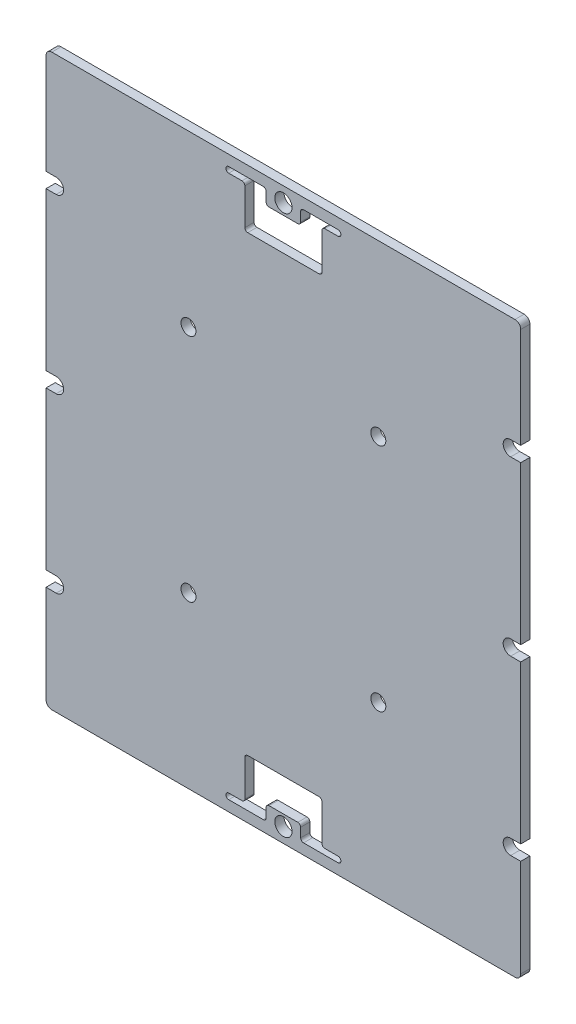
SolidWorks part; units mm, degrees
material "FR4_stuffedProtoboard"
ref_plane "Front Plane" through (0, 0, 0) normal (0, 0, 1) x (1, 0, 0)
ref_plane "Top Plane" through (0, 0, 0) normal (0, 1, 0) x (1, 0, 0)
ref_plane "Right Plane" through (0, 0, 0) normal (1, 0, 0) x (0, 0, -1)
sketch "Sketch2" plane through (0, 0, 0) normal (0, 0, 1) x (1, 0, 0)
  line L0 (39.5, 49.75) -> (-39.5, 49.75) construction
  line L1 (-41.5, 49.75) -> (41.5, 49.75) construction
  line L2 (-41.5, 49.75) -> (-41.5, -49.75) construction
  line L3 (-41.5, -49.75) -> (41.5, -49.75) construction
  line L4 (41.5, 49.75) -> (41.5, -49.75) construction
  line L5 (-41.5, 49.75) -> (41.5, -49.75) construction
  line L6 (-41.5, -49.75) -> (41.5, 49.75) construction
  line L7 (41.5, 51.75) -> (41.5, 40.35) construction
  line L8 (-41.5, 49.75) -> (41.5, 49.75) construction
  line L9 (41.5, 49.75) -> (41.5, -49.75) construction
  line L10 (-41.5, -49.75) -> (41.5, -49.75) construction
  line L11 (-41.5, 49.75) -> (-41.5, -49.75) construction
  line L12 (-37, -31.85) -> (37, -31.85) construction
  line L13 (-37, -30.25) -> (37, -30.25) construction
  line L14 (-37, -21.85) -> (37, -21.85) construction
  line L15 (-37, -20.25) -> (37, -20.25) construction
  line L16 (-37, -11.85) -> (37, -11.85) construction
  line L17 (-37, -10.25) -> (37, -10.25) construction
  line L18 (-37, -1.85) -> (37, -1.85) construction
  line L19 (-37, -0.25) -> (37, -0.25) construction
  line L20 (-37, 8.15) -> (37, 8.15) construction
  line L21 (-37, 9.75) -> (37, 9.75) construction
  line L22 (-37, 18.15) -> (37, 18.15) construction
  line L23 (-37, 19.75) -> (37, 19.75) construction
  line L24 (-37, 28.15) -> (37, 28.15) construction
  line L25 (-37, 29.75) -> (37, 29.75) construction
  line L26 (-37, 38.15) -> (37, 38.15) construction
  line L27 (-37, 39.75) -> (37, 39.75) construction
  line L28 (-37, -31.85) -> (37, -31.85) construction
  line L29 (-37, -30.25) -> (37, -30.25) construction
  line L30 (-37, -21.85) -> (37, -21.85) construction
  line L31 (-37, -20.25) -> (37, -20.25) construction
  line L32 (-37, -11.85) -> (37, -11.85) construction
  line L33 (-37, -10.25) -> (37, -10.25) construction
  line L34 (-37, -1.85) -> (37, -1.85) construction
  line L35 (-37, -0.25) -> (37, -0.25) construction
  line L36 (-37, 8.15) -> (37, 8.15) construction
  line L37 (-37, 9.75) -> (37, 9.75) construction
  line L38 (-37, 18.15) -> (37, 18.15) construction
  line L39 (-37, 19.75) -> (37, 19.75) construction
  line L40 (-37, 28.15) -> (37, 28.15) construction
  line L41 (-37, 29.75) -> (37, 29.75) construction
  line L42 (-37, 38.15) -> (37, 38.15) construction
  line L43 (-37, 39.75) -> (37, 39.75) construction
  line L44 (-37, -40.25) -> (37, -40.25) construction
  line L45 (-37, -41.85) -> (37, -41.85) construction
  line L46 (-41.5, 51.75) -> (-41.5, 40.35) construction
  line L47 (39.5, -49.75) -> (-39.5, -49.75) construction
  line L48 (41.5, -31.9) -> (41.5, -51.75) construction
  line L49 (-41.25, 49.5) -> (41.25, 49.5)
  line L50 (41.25, 49.5) -> (41.25, -49.5)
  line L51 (-41.25, -49.5) -> (41.25, -49.5)
  line L52 (-41.25, 49.5) -> (-41.25, -49.5)
  circle A0 centre (0, 46.95) radius 1.5 construction
  circle A1 centre (0, 46.95) radius 0.8 construction
  circle A2 centre (0, 46.95) radius 1.5 construction
  circle A3 centre (0, 46.95) radius 0.8
  circle A4 centre (-39.5, -30.25) radius 0.8 construction
  circle A5 centre (-39.5, -0.25) radius 0.8 construction
  circle A6 centre (-39.5, 29.75) radius 0.8 construction
  circle A7 centre (-39.5, -30.25) radius 0.8
  circle A8 centre (-39.5, -0.25) radius 0.8
  circle A9 centre (-39.5, 29.75) radius 0.8
  circle A10 centre (39.5, -30.25) radius 0.8 construction
  circle A11 centre (39.5, -0.25) radius 0.8 construction
  circle A12 centre (39.5, 29.75) radius 0.8 construction
  circle A13 centre (39.5, -30.25) radius 0.8
  circle A14 centre (39.5, -0.25) radius 0.8
  circle A15 centre (39.5, 29.75) radius 0.8
  circle A16 centre (0, -46.95) radius 0.8 construction
  circle A17 centre (0, -46.95) radius 0.8
  circle A18 centre (0, -46.95) radius 1.5 construction
  circle A19 centre (0, -46.95) radius 1.5
  circle A20 centre (-16.5, 20) radius 1.75 construction
  circle A21 centre (-16.5, 20) radius 0.8 construction
  circle A22 centre (-16.5, 20) radius 1.75 construction
  circle A23 centre (-16.5, 20) radius 0.8
  circle A24 centre (16.5, 20) radius 1.75 construction
  circle A25 centre (16.5, 20) radius 0.8 construction
  circle A26 centre (16.5, 20) radius 1.75 construction
  circle A27 centre (16.5, 20) radius 0.8
  circle A28 centre (16.5, -20) radius 1.75 construction
  circle A29 centre (-16.5, -20) radius 1.75 construction
  circle A30 centre (16.5, -20) radius 1.75 construction
  circle A31 centre (-16.5, -20) radius 1.75 construction
  circle A32 centre (-16.5, -20) radius 0.8 construction
  circle A33 centre (-16.5, -20) radius 0.8
  circle A34 centre (16.5, -20) radius 0.8 construction
  circle A35 centre (16.5, -20) radius 0.8
  point P0 (0, 0)
  point P74 (0, -40.25)
  point P75 (0, -31.85)
  point P76 (0, -41.85)
  dimension "D2" = 10
  dimension "D3" = 1.6
  dimension "D1" = 0.25
extrude "pcb extrude" add sketch "Sketch2" along normal mid plane 1.6 contours L4 L1 L2 L3 A2 | A2 A3 | L2 L1 L4 L3 region at (0, 0.0296, 0)
sketch "endcap connector" plane through (0, 0, 0.8) normal (0, 0, 1) x (1, 0, 0)
  line L0 (-10.3489, -47.209) -> (-10.3489, -49.749) construction
  line L1 (-36.1289, -47.209) -> (-10.3489, -47.209) construction
  line L2 (-36.1289, -47.209) -> (-10.3489, -47.209)
  line L3 (-36.1289, -49.749) -> (-36.1289, -47.209) construction
  line L4 (-10.3489, -47.209) -> (-10.3489, -49.749)
  line L5 (-36.1289, -49.749) -> (-36.1289, -47.209)
  point P3 (-23.2389, -47.209)
sketch "connector locations" plane through (0, 0, 0.8) normal (0, 0, 1) x (1, 0, 0)
  line L0 (34.5, 45.75) -> (4.5, 45.75) construction
  line L1 (-2.5, 44.75) -> (2.5, 44.75) construction
  line L2 (-4.5, 45.75) -> (-34.5, 45.75) construction
  line L3 (34.5, 45.75) -> (4.5, 45.75)
  line L4 (-2.5, 44.75) -> (2.5, 44.75)
  line L5 (-4.5, 45.75) -> (-34.5, 45.75)
  line L6 (-37, 43.25) -> (-37, -43.25) construction
  line L7 (-37, 43.25) -> (-37, -43.25)
  line L8 (37, -43.25) -> (37, 43.25) construction
  line L9 (37, -43.25) -> (37, 43.25)
  line L10 (4.5, -45.75) -> (34.5, -45.75) construction
  line L11 (4.5, -45.75) -> (34.5, -45.75)
  line L12 (-34.5, -45.75) -> (-4.5, -45.75) construction
  line L13 (-2.5, -44.75) -> (2.5, -44.75) construction
  line L14 (-34.5, -45.75) -> (-4.5, -45.75)
  line L15 (-2.5, -44.75) -> (2.5, -44.75)
  line L16 (-37, 39.75) -> (37, 39.75) construction
  line L17 (-33.9182, 41.909) -> (-9.2802, 41.909)
  line L18 (-33.9182, 41.909) -> (-33.9182, 43.306)
  line L19 (-33.9182, 43.306) -> (-9.2802, 43.306)
  line L20 (-9.2802, 41.909) -> (-9.2802, 43.306)
  line L21 (-33.9182, 41.909) -> (-9.2802, 43.306) construction
  line L22 (-33.9182, 43.306) -> (-9.2802, 41.909) construction
  line L23 (-33.9182, 33.306) -> (-22.0818, 33.306)
  line L24 (-33.9182, 33.306) -> (-33.9182, 31.909)
  line L25 (-33.9182, 31.909) -> (-22.0818, 31.909)
  line L26 (-22.0818, 33.306) -> (-22.0818, 31.909)
  line L27 (-33.9182, 33.306) -> (-22.0818, 31.909) construction
  line L28 (-33.9182, 31.909) -> (-22.0818, 33.306) construction
  line L29 (-12.319, 33.306) -> (12.319, 33.306)
  line L30 (-12.319, 33.306) -> (-12.319, 31.909)
  line L31 (-12.319, 31.909) -> (12.319, 31.909)
  line L32 (12.319, 33.306) -> (12.319, 31.909)
  line L33 (-12.319, 33.306) -> (12.319, 31.909) construction
  line L34 (-12.319, 31.909) -> (12.319, 33.306) construction
  line L35 (-33.9182, 23.306) -> (-22.0818, 23.306)
  line L36 (-33.9182, 23.306) -> (-33.9182, 21.909)
  line L37 (-33.9182, 21.909) -> (-22.0818, 21.909)
  line L38 (-33.9182, 23.306) -> (-22.0818, 21.909) construction
  line L39 (-33.9182, 21.909) -> (-22.0818, 23.306) construction
  line L40 (-22.0818, 23.306) -> (-22.0818, 21.909)
  line L41 (-12.319, 23.306) -> (-12.319, 21.909)
  line L42 (-12.319, 23.306) -> (12.319, 23.306)
  line L43 (-12.319, 21.909) -> (12.319, 21.909)
  line L44 (-12.319, 23.306) -> (12.319, 21.909) construction
  line L45 (-12.319, 21.909) -> (12.319, 23.306) construction
  line L46 (12.319, 23.306) -> (12.319, 21.909)
  line L47 (-33.9182, 13.306) -> (-22.0818, 13.306)
  line L48 (-33.9182, 13.306) -> (-33.9182, 11.909)
  line L49 (-33.9182, 11.909) -> (-22.0818, 11.909)
  line L50 (-33.9182, 13.306) -> (-22.0818, 11.909) construction
  line L51 (-33.9182, 11.909) -> (-22.0818, 13.306) construction
  line L52 (-22.0818, 13.306) -> (-22.0818, 11.909)
  line L53 (-12.319, 13.306) -> (-12.319, 11.909)
  line L54 (-12.319, 13.306) -> (12.319, 13.306)
  line L55 (-12.319, 11.909) -> (12.319, 11.909)
  line L56 (-12.319, 13.306) -> (12.319, 11.909) construction
  line L57 (-12.319, 11.909) -> (12.319, 13.306) construction
  line L58 (12.319, 13.306) -> (12.319, 11.909)
  line L59 (-33.9182, 3.306) -> (-22.0818, 3.306)
  line L60 (-33.9182, 3.306) -> (-33.9182, 1.909)
  line L61 (-33.9182, 1.909) -> (-22.0818, 1.909)
  line L62 (-33.9182, 3.306) -> (-22.0818, 1.909) construction
  line L63 (-33.9182, 1.909) -> (-22.0818, 3.306) construction
  line L64 (-22.0818, 3.306) -> (-22.0818, 1.909)
  line L65 (-12.319, 3.306) -> (-12.319, 1.909)
  line L66 (-12.319, 3.306) -> (12.319, 3.306)
  line L67 (-12.319, 1.909) -> (12.319, 1.909)
  line L68 (-12.319, 3.306) -> (12.319, 1.909) construction
  line L69 (-12.319, 1.909) -> (12.319, 3.306) construction
  line L70 (12.319, 3.306) -> (12.319, 1.909)
  line L71 (-33.9182, -6.694) -> (-22.0818, -6.694)
  line L72 (-33.9182, -6.694) -> (-33.9182, -8.091)
  line L73 (-33.9182, -8.091) -> (-22.0818, -8.091)
  line L74 (-33.9182, -6.694) -> (-22.0818, -8.091) construction
  line L75 (-33.9182, -8.091) -> (-22.0818, -6.694) construction
  line L76 (-22.0818, -6.694) -> (-22.0818, -8.091)
  line L77 (-12.319, -6.694) -> (-12.319, -8.091)
  line L78 (-12.319, -6.694) -> (12.319, -6.694)
  line L79 (-12.319, -8.091) -> (12.319, -8.091)
  line L80 (-12.319, -6.694) -> (12.319, -8.091) construction
  line L81 (-12.319, -8.091) -> (12.319, -6.694) construction
  line L82 (12.319, -6.694) -> (12.319, -8.091)
  line L83 (-33.9182, -16.694) -> (-22.0818, -16.694)
  line L84 (-33.9182, -16.694) -> (-33.9182, -18.091)
  line L85 (-33.9182, -18.091) -> (-22.0818, -18.091)
  line L86 (-33.9182, -16.694) -> (-22.0818, -18.091) construction
  line L87 (-33.9182, -18.091) -> (-22.0818, -16.694) construction
  line L88 (-22.0818, -16.694) -> (-22.0818, -18.091)
  line L89 (-12.319, -16.694) -> (-12.319, -18.091)
  line L90 (-12.319, -16.694) -> (12.319, -16.694)
  line L91 (-12.319, -18.091) -> (12.319, -18.091)
  line L92 (-12.319, -16.694) -> (12.319, -18.091) construction
  line L93 (-12.319, -18.091) -> (12.319, -16.694) construction
  line L94 (12.319, -16.694) -> (12.319, -18.091)
  line L95 (-33.9182, -26.694) -> (-22.0818, -26.694)
  line L96 (-33.9182, -26.694) -> (-33.9182, -28.091)
  line L97 (-33.9182, -28.091) -> (-22.0818, -28.091)
  line L98 (-33.9182, -26.694) -> (-22.0818, -28.091) construction
  line L99 (-33.9182, -28.091) -> (-22.0818, -26.694) construction
  line L100 (-22.0818, -26.694) -> (-22.0818, -28.091)
  line L101 (-12.319, -26.694) -> (-12.319, -28.091)
  line L102 (-12.319, -26.694) -> (12.319, -26.694)
  line L103 (-12.319, -28.091) -> (12.319, -28.091)
  line L104 (-12.319, -26.694) -> (12.319, -28.091) construction
  line L105 (-12.319, -28.091) -> (12.319, -26.694) construction
  line L106 (12.319, -26.694) -> (12.319, -28.091)
  line L110 (-35.1136, -38.0476) -> (-35.52, -38.0476) construction
  line L111 (-35.5089, -38.2476) -> (-10.9689, -38.2476)
  line L116 (-35.5089, -38.2476) -> (-35.5089, -38.0476)
  line L117 (-35.5089, -38.0476) -> (-10.9689, -38.0476)
  line L119 (0, 32.6075) -> (0, 22.6075) construction
  line L120 (-37, 29.75) -> (37, 29.75) construction
  line L121 (32.92, 41.02) -> (35.08, 38.84) construction
  line L122 (32.92, 38.84) -> (35.08, 41.02) construction
  line L123 (26.92, 38.84) -> (29.08, 41.02) construction
  line L124 (26.92, 41.02) -> (29.08, 38.84) construction
  line L125 (20.92, 38.84) -> (23.08, 41.02) construction
  line L126 (20.92, 41.02) -> (23.08, 38.84) construction
  line L127 (26.92, 28.84) -> (29.08, 31.02) construction
  line L128 (26.92, 31.02) -> (29.08, 28.84) construction
  line L129 (20.92, 28.84) -> (23.08, 31.02) construction
  line L130 (20.92, 31.02) -> (23.08, 28.84) construction
  line L131 (26.92, 18.84) -> (29.08, 21.02) construction
  line L132 (26.92, 21.02) -> (29.08, 18.84) construction
  line L133 (20.92, 18.84) -> (23.08, 21.02) construction
  line L134 (20.92, 21.02) -> (23.08, 18.84) construction
  line L135 (26.92, 8.84) -> (29.08, 11.02) construction
  line L136 (26.92, 11.02) -> (29.08, 8.84) construction
  line L137 (20.92, 8.84) -> (23.08, 11.02) construction
  line L138 (20.92, 11.02) -> (23.08, 8.84) construction
  line L139 (26.92, -1.16) -> (29.08, 1.02) construction
  line L140 (26.92, 1.02) -> (29.08, -1.16) construction
  line L141 (20.92, -1.16) -> (23.08, 1.02) construction
  line L142 (20.92, 1.02) -> (23.08, -1.16) construction
  line L143 (26.92, -11.16) -> (29.08, -8.98) construction
  line L144 (26.92, -8.98) -> (29.08, -11.16) construction
  line L145 (20.92, -11.16) -> (23.08, -8.98) construction
  line L146 (20.92, -8.98) -> (23.08, -11.16) construction
  line L147 (26.92, -21.16) -> (29.08, -18.98) construction
  line L148 (26.92, -18.98) -> (29.08, -21.16) construction
  line L149 (20.92, -21.16) -> (23.08, -18.98) construction
  line L150 (20.92, -18.98) -> (23.08, -21.16) construction
  line L151 (26.92, -31.16) -> (29.08, -28.98) construction
  line L152 (26.92, -28.98) -> (29.08, -31.16) construction
  line L153 (20.92, -31.16) -> (23.08, -28.98) construction
  line L154 (20.92, -28.98) -> (23.08, -31.16) construction
  line L155 (26.92, -41.16) -> (29.08, -38.98) construction
  line L156 (26.92, -38.98) -> (29.08, -41.16) construction
  line L157 (20.92, -41.16) -> (23.08, -38.98) construction
  line L158 (20.92, -38.98) -> (23.08, -41.16) construction
  line L159 (32.92, 28.84) -> (35.08, 31.02) construction
  line L160 (32.92, 31.02) -> (35.08, 28.84) construction
  line L161 (32.92, 18.84) -> (35.08, 21.02) construction
  line L162 (32.92, 21.02) -> (35.08, 18.84) construction
  line L163 (32.92, 8.84) -> (35.08, 11.02) construction
  line L164 (32.92, 11.02) -> (35.08, 8.84) construction
  line L165 (32.92, -1.16) -> (35.08, 1.02) construction
  line L166 (32.92, 1.02) -> (35.08, -1.16) construction
  line L167 (32.92, -11.16) -> (35.08, -8.98) construction
  line L168 (32.92, -8.98) -> (35.08, -11.16) construction
  line L169 (32.92, -21.16) -> (35.08, -18.98) construction
  line L170 (32.92, -18.98) -> (35.08, -21.16) construction
  line L171 (32.92, -31.16) -> (35.08, -28.98) construction
  line L172 (32.92, -28.98) -> (35.08, -31.16) construction
  line L173 (32.92, -41.16) -> (35.08, -38.98) construction
  line L174 (32.92, -38.98) -> (35.08, -41.16) construction
  line L175 (34, 39.93) -> (28, 39.93) construction
  line L176 (34, 39.93) -> (34, 29.93) construction
  line L182 (-10.9689, -38.2476) -> (-10.9689, -38.0476)
  line L183 (-35.5089, -38.2476) -> (-10.9689, -38.0476) construction
  line L184 (-35.5089, -38.0476) -> (-10.9689, -38.2476) construction
  arc A0 (4.5, 45.75) -> (2.5, 44.75) centre (4.5, 43.25) ccw construction
  arc A1 (-2.5, 44.75) -> (-4.5, 45.75) centre (-4.5, 43.25) ccw construction
  arc A2 (-34.5, 45.75) -> (-37, 43.25) centre (-34.5, 43.25) ccw construction
  arc A3 (4.5, 45.75) -> (2.5, 44.75) centre (4.5, 43.25) ccw
  arc A4 (-2.5, 44.75) -> (-4.5, 45.75) centre (-4.5, 43.25) ccw
  arc A5 (-34.5, 45.75) -> (-37, 43.25) centre (-34.5, 43.25) ccw
  arc A6 (37, 43.25) -> (34.5, 45.75) centre (34.5, 43.25) ccw construction
  arc A7 (37, 43.25) -> (34.5, 45.75) centre (34.5, 43.25) ccw
  arc A8 (34.5, -45.75) -> (37, -43.25) centre (34.5, -43.25) ccw construction
  arc A9 (34.5, -45.75) -> (37, -43.25) centre (34.5, -43.25) ccw
  arc A10 (-37, -43.25) -> (-34.5, -45.75) centre (-34.5, -43.25) ccw construction
  arc A11 (-4.5, -45.75) -> (-2.5, -44.75) centre (-4.5, -43.25) ccw construction
  arc A12 (2.5, -44.75) -> (4.5, -45.75) centre (4.5, -43.25) ccw construction
  arc A13 (-37, -43.25) -> (-34.5, -45.75) centre (-34.5, -43.25) ccw
  arc A14 (-4.5, -45.75) -> (-2.5, -44.75) centre (-4.5, -43.25) ccw
  arc A15 (2.5, -44.75) -> (4.5, -45.75) centre (4.5, -43.25) ccw
  circle A16 centre (-21.5992, 42.6075) radius 0.5
  circle A17 centre (0, 32.6075) radius 0.5
  circle A18 centre (-28, 32.6075) radius 0.5
  circle A19 centre (-28, 22.6075) radius 0.5
  circle A20 centre (0, 22.6075) radius 0.5
  circle A21 centre (-28, 12.6075) radius 0.5
  circle A22 centre (0, 12.6075) radius 0.5
  circle A23 centre (-28, 2.6075) radius 0.5
  circle A24 centre (0, 2.6075) radius 0.5
  circle A25 centre (-28, -7.3925) radius 0.5
  circle A26 centre (0, -7.3925) radius 0.5
  circle A27 centre (-28, -17.3925) radius 0.5
  circle A28 centre (0, -17.3925) radius 0.5
  circle A29 centre (-28, -27.3925) radius 0.5
  circle A30 centre (0, -27.3925) radius 0.5
  circle A33 centre (35.08, 41.02) radius 0.32
  circle A34 centre (32.92, 38.84) radius 0.32
  circle A35 centre (35.08, 38.84) radius 0.32
  circle A36 centre (32.92, 41.02) radius 0.32
  circle A37 centre (26.92, 41.02) radius 0.32
  circle A38 centre (29.08, 41.02) radius 0.32
  circle A39 centre (26.92, 38.84) radius 0.32
  circle A40 centre (29.08, 38.84) radius 0.32
  circle A41 centre (20.92, 41.02) radius 0.32
  circle A42 centre (23.08, 41.02) radius 0.32
  circle A43 centre (20.92, 38.84) radius 0.32
  circle A44 centre (23.08, 38.84) radius 0.32
  circle A45 centre (26.92, 31.02) radius 0.32
  circle A46 centre (29.08, 31.02) radius 0.32
  circle A47 centre (26.92, 28.84) radius 0.32
  circle A48 centre (29.08, 28.84) radius 0.32
  circle A49 centre (20.92, 31.02) radius 0.32
  circle A50 centre (23.08, 31.02) radius 0.32
  circle A51 centre (20.92, 28.84) radius 0.32
  circle A52 centre (23.08, 28.84) radius 0.32
  circle A53 centre (26.92, 21.02) radius 0.32
  circle A54 centre (29.08, 21.02) radius 0.32
  circle A55 centre (26.92, 18.84) radius 0.32
  circle A56 centre (29.08, 18.84) radius 0.32
  circle A57 centre (20.92, 21.02) radius 0.32
  circle A58 centre (23.08, 21.02) radius 0.32
  circle A59 centre (20.92, 18.84) radius 0.32
  circle A60 centre (23.08, 18.84) radius 0.32
  circle A61 centre (26.92, 11.02) radius 0.32
  circle A62 centre (29.08, 11.02) radius 0.32
  circle A63 centre (26.92, 8.84) radius 0.32
  circle A64 centre (29.08, 8.84) radius 0.32
  circle A65 centre (20.92, 11.02) radius 0.32
  circle A66 centre (23.08, 11.02) radius 0.32
  circle A67 centre (20.92, 8.84) radius 0.32
  circle A68 centre (23.08, 8.84) radius 0.32
  circle A69 centre (26.92, 1.02) radius 0.32
  circle A70 centre (29.08, 1.02) radius 0.32
  circle A71 centre (26.92, -1.16) radius 0.32
  circle A72 centre (29.08, -1.16) radius 0.32
  circle A73 centre (20.92, 1.02) radius 0.32
  circle A74 centre (23.08, 1.02) radius 0.32
  circle A75 centre (20.92, -1.16) radius 0.32
  circle A76 centre (23.08, -1.16) radius 0.32
  circle A77 centre (26.92, -8.98) radius 0.32
  circle A78 centre (29.08, -8.98) radius 0.32
  circle A79 centre (26.92, -11.16) radius 0.32
  circle A80 centre (29.08, -11.16) radius 0.32
  circle A81 centre (20.92, -8.98) radius 0.32
  circle A82 centre (23.08, -8.98) radius 0.32
  circle A83 centre (20.92, -11.16) radius 0.32
  circle A84 centre (23.08, -11.16) radius 0.32
  circle A85 centre (26.92, -18.98) radius 0.32
  circle A86 centre (29.08, -18.98) radius 0.32
  circle A87 centre (26.92, -21.16) radius 0.32
  circle A88 centre (29.08, -21.16) radius 0.32
  circle A89 centre (20.92, -18.98) radius 0.32
  circle A90 centre (23.08, -18.98) radius 0.32
  circle A91 centre (20.92, -21.16) radius 0.32
  circle A92 centre (23.08, -21.16) radius 0.32
  circle A93 centre (26.92, -28.98) radius 0.32
  circle A94 centre (29.08, -28.98) radius 0.32
  circle A95 centre (26.92, -31.16) radius 0.32
  circle A96 centre (29.08, -31.16) radius 0.32
  circle A97 centre (20.92, -28.98) radius 0.32
  circle A98 centre (23.08, -28.98) radius 0.32
  circle A99 centre (20.92, -31.16) radius 0.32
  circle A100 centre (23.08, -31.16) radius 0.32
  circle A101 centre (26.92, -38.98) radius 0.32
  circle A102 centre (29.08, -38.98) radius 0.32
  circle A103 centre (26.92, -41.16) radius 0.32
  circle A104 centre (29.08, -41.16) radius 0.32
  circle A105 centre (20.92, -38.98) radius 0.32
  circle A106 centre (23.08, -38.98) radius 0.32
  circle A107 centre (20.92, -41.16) radius 0.32
  circle A108 centre (23.08, -41.16) radius 0.32
  circle A109 centre (32.92, 31.02) radius 0.32
  circle A110 centre (35.08, 31.02) radius 0.32
  circle A111 centre (32.92, 28.84) radius 0.32
  circle A112 centre (35.08, 28.84) radius 0.32
  circle A113 centre (32.92, 21.02) radius 0.32
  circle A114 centre (35.08, 21.02) radius 0.32
  circle A115 centre (32.92, 18.84) radius 0.32
  circle A116 centre (35.08, 18.84) radius 0.32
  circle A117 centre (32.92, 11.02) radius 0.32
  circle A118 centre (35.08, 11.02) radius 0.32
  circle A119 centre (32.92, 8.84) radius 0.32
  circle A120 centre (35.08, 8.84) radius 0.32
  circle A121 centre (32.92, 1.02) radius 0.32
  circle A122 centre (35.08, 1.02) radius 0.32
  circle A123 centre (32.92, -1.16) radius 0.32
  circle A124 centre (35.08, -1.16) radius 0.32
  circle A125 centre (32.92, -8.98) radius 0.32
  circle A126 centre (35.08, -8.98) radius 0.32
  circle A127 centre (32.92, -11.16) radius 0.32
  circle A128 centre (35.08, -11.16) radius 0.32
  circle A129 centre (32.92, -18.98) radius 0.32
  circle A130 centre (35.08, -18.98) radius 0.32
  circle A131 centre (32.92, -21.16) radius 0.32
  circle A132 centre (35.08, -21.16) radius 0.32
  circle A133 centre (32.92, -28.98) radius 0.32
  circle A134 centre (35.08, -28.98) radius 0.32
  circle A135 centre (32.92, -31.16) radius 0.32
  circle A136 centre (35.08, -31.16) radius 0.32
  circle A137 centre (32.92, -38.98) radius 0.32
  circle A138 centre (35.08, -38.98) radius 0.32
  circle A139 centre (32.92, -41.16) radius 0.32
  circle A140 centre (35.08, -41.16) radius 0.32
  point P18 (-21.5992, 42.6075)
  point P29 (-28, 32.6075)
  point P34 (0, 32.6075)
  point P50 (-28, 22.6075)
  point P55 (0, 22.6075)
  point P64 (-28, 12.6075)
  point P69 (0, 12.6075)
  point P78 (-28, 2.6075)
  point P83 (0, 2.6075)
  point P92 (-28, -7.3925)
  point P97 (0, -7.3925)
  point P106 (-28, -17.3925)
  point P111 (0, -17.3925)
  point P120 (-28, -27.3925)
  point P125 (0, -27.3925)
  point P134 (-23.2389, -38.1476)
  point P136 (-23.2389, -38.1476)
  point P165 (34, 39.93)
  point P170 (28, 39.93)
  point P179 (22, 39.93)
  point P188 (28, 29.93)
  point P197 (22, 29.93)
  point P206 (28, 19.93)
  point P215 (22, 19.93)
  point P224 (28, 9.93)
  point P233 (22, 9.93)
  point P242 (28, -0.07)
  point P251 (22, -0.07)
  point P260 (28, -10.07)
  point P269 (22, -10.07)
  point P278 (28, -20.07)
  point P287 (22, -20.07)
  point P296 (28, -30.07)
  point P305 (22, -30.07)
  point P314 (28, -40.07)
  point P323 (22, -40.07)
  point P332 (34, 29.93)
  point P341 (34, 19.93)
  point P350 (34, 9.93)
  point P359 (34, -0.07)
  point P368 (34, -10.07)
  point P377 (34, -20.07)
  point P386 (34, -30.07)
  point P395 (34, -40.07)
  dimension "D4" = 1
  dimension "D5" = 11.8364
  dimension "D10" = 0.64
  dimension "D1" = 24.638
  dimension "D2" = 1.397
  dimension "D3" = 2.159
  dimension "D6" = 28
  dimension "D8" = 10
  dimension "D9" = 2.159
  dimension "D11" = 2.18
  dimension "D12" = 2.16
  dimension "D13" = 0.18
  dimension "D14" = 34
  dimension "D17" = 6
  dimension "D18" = 10
  dimension "D24" = 24.54
  dimension "D25" = 0.2
  dimension "D7" = 7
  dimension "D15" = 3
  dimension "D16" = 9
fillet "corner fillets" radius 1 4 edges at (41.25, -49.5, 0) (-41.25, -49.5, 0) (41.25, 49.5, 0) (-41.25, 49.5, 0)
sketch "Sketch4" plane through (0, 0, 0.8) normal (0, 0, 1) x (1, 0, 0)
  line L0 (0, 46.95) -> (0, 39.35) construction
  line L1 (6.7, 39.35) -> (-6.7, 39.35)
  line L2 (-6.7, 39.35) -> (-6.7, 46.65)
  line L3 (-6.7, 46.65) -> (-9.5, 46.65)
  line L4 (-4.5, 45.75) -> (-34.5, 45.75) construction
  line L5 (-9.5, 47.65) -> (-3, 47.65)
  line L6 (-3, 47.65) -> (-3, 45.05)
  line L7 (-3, 45.05) -> (3, 45.05)
  line L8 (3, 47.65) -> (3, 45.05)
  line L9 (6.7, 39.35) -> (6.7, 46.65)
  line L10 (6.7, 46.65) -> (9.5, 46.65)
  line L11 (9.5, 47.65) -> (3, 47.65)
  line L12 (0.88, 0) -> (-0.88, 0) construction
  line L13 (6.7, -46.65) -> (9.5, -46.65)
  line L14 (9.5, -47.65) -> (3, -47.65)
  line L15 (3, -47.65) -> (3, -45.05)
  line L16 (-3, -45.05) -> (3, -45.05)
  line L17 (-3, -47.65) -> (-3, -45.05)
  line L18 (-9.5, -47.65) -> (-3, -47.65)
  line L19 (-6.7, -46.65) -> (-9.5, -46.65)
  line L20 (-6.7, -39.35) -> (-6.7, -46.65)
  line L21 (6.7, -39.35) -> (-6.7, -39.35)
  line L22 (6.7, -39.35) -> (6.7, -46.65)
  arc A0 (-9.5, 47.65) -> (-9.5, 46.65) centre (-9.5, 47.15) ccw
  arc A1 (9.5, 47.65) -> (9.5, 46.65) centre (9.5, 47.15) cw
  circle A2 centre (0, 46.95) radius 1.5
  arc A3 (9.5, -47.65) -> (9.5, -46.65) centre (9.5, -47.15) ccw
  arc A4 (-9.5, -47.65) -> (-9.5, -46.65) centre (-9.5, -47.15) cw
  point P17 (0, 45.05)
  dimension "D3" = 1
  dimension "D8" = 3
  dimension "D1" = 3
  dimension "D2" = 9.5
  dimension "D4" = 0.9
  dimension "D5" = 7.3
  dimension "D6" = 2.6
  dimension "D7" = 3.7
extrude "solar holes" cut sketch "Sketch4" against normal through all
fillet "solar hole fillets" radius 0.5 16 edges at (6.7, 46.65, 0) (3, 47.65, 0) (3, 45.05, 0) (6.7, 39.35, 0) (-6.7, 39.35, 0) (-6.7, 46.65, 0) (-3, 45.05, 0) (-3, 47.65, 0) (3, -47.65, 0) (3, -45.05, 0) (-3, -47.65, 0) (-3, -45.05, 0) (-6.7, -46.65, 0) (6.7, -46.65, 0) (6.7, -39.35, 0) (-6.7, -39.35, 0)
sketch "m2 locations" plane through (0, 0, 0.8) normal (0, 0, 1) x (1, 0, 0)
  point P0 (-39.5, 29.75)
  point P1 (-39.5, -0.25)
  point P3 (-39.5, -30.25)
  point P5 (-16.5, -20)
  point P7 (-16.5, 20)
  point P9 (16.5, 20)
  point P11 (16.5, -20)
  point P13 (39.5, -30.25)
  point P15 (39.5, -0.25)
  point P17 (39.5, 29.75)
hole_wizard "M2 Clearance Holes" positions "Sketch8" profile "Sketch9" hole size "M2" standard "ANSI Metric" end condition through all
sketch "Sketch8" plane through (0, 0, 0.8) normal (0, 0, 1) x (1, 0, 0)
  point P0 (-39.5, 29.75)
  point P3 (-39.5, -0.25)
  point P6 (-16.5, 20)
  point P9 (16.5, 20)
  point P12 (16.5, -20)
  point P15 (-16.5, -20)
  point P18 (39.5, 29.75)
  point P21 (39.5, -0.25)
  point P24 (39.5, -30.25)
  point P27 (-39.5, -30.25)
sketch "Sketch9" plane through (-39.5, 29.75, 0.8) normal (1, 0, 0) x (0, -1, 0)
  line L0 (0, 0) -> (0, 1.6)
  line L1 (0, 1.6) -> (1.3, 1.6)
  line L2 (1.3, 1.6) -> (1.3, 0)
  line L5 (1.3, 0) -> (0, 0)
  line L11 (0, -6.35) -> (0, 107.95) construction
  dimension "Thru Hole Dia." = 2.6
  dimension "Thru Hole Depth" = 1.6
sketch "Sketch10" plane through (0, 0, 0.8) normal (0, 0, 1) x (1, 0, 0)
  line L0 (-41.25, 48.5) -> (-41.25, -48.5) construction
  line L1 (-39.5, 31.05) -> (-41.25, 31.05)
  line L2 (-39.5, 31.05) -> (-39.5, 28.45)
  line L3 (-39.5, 28.45) -> (-41.25, 28.45)
  line L4 (-41.25, 31.05) -> (-41.25, 28.45)
  line L5 (41.25, 48.5) -> (41.25, -48.5) construction
  line L6 (-39.5, 1.05) -> (-41.25, 1.05)
  line L7 (-39.5, 1.05) -> (-39.5, -1.55)
  line L8 (-39.5, -1.55) -> (-41.25, -1.55)
  line L9 (-41.25, 1.05) -> (-41.25, -1.55)
  line L10 (-39.5, -28.95) -> (-41.25, -28.95)
  line L11 (-39.5, -28.95) -> (-39.5, -31.55)
  line L12 (-39.5, -31.55) -> (-41.25, -31.55)
  line L13 (-41.25, -28.95) -> (-41.25, -31.55)
  line L14 (39.5, -28.95) -> (41.25, -28.95)
  line L15 (39.5, -28.95) -> (39.5, -31.55)
  line L16 (39.5, -31.55) -> (41.25, -31.55)
  line L17 (41.25, -28.95) -> (41.25, -31.55)
  line L19 (39.5, 1.05) -> (41.25, 1.05)
  line L20 (39.5, 1.05) -> (39.5, -1.55)
  line L21 (39.5, -1.55) -> (41.25, -1.55)
  line L22 (41.25, 1.05) -> (41.25, -1.55)
  line L23 (39.5, 31.05) -> (41.25, 31.05)
  line L24 (39.5, 31.05) -> (39.5, 28.45)
  line L25 (39.5, 28.45) -> (41.25, 28.45)
  line L26 (41.25, 31.05) -> (41.25, 28.45)
  circle A0 centre (-39.5, 29.75) radius 1.3 construction
  circle A1 centre (-39.5, -0.25) radius 1.3 construction
  circle A2 centre (-39.5, -30.25) radius 1.3 construction
  circle A3 centre (39.5, -30.25) radius 1.3 construction
  circle A4 centre (39.5, -0.25) radius 1.3 construction
  circle A5 centre (39.5, 29.75) radius 1.3 construction
  point P43 (-39.5, 29.75)
extrude "Cut-Extrude2" cut sketch "Sketch10" against normal through all
sketch "Debug Cutout" plane through (0, 0, 0.8) normal (0, 0, 1) x (1, 0, 0)
  line L0 (-37, -6.25) -> (-37, 5.75) construction
  line L17 (-29.5, -8.25) -> (-35, -8.25) construction
  line L18 (-35, 7.75) -> (-29.5, 7.75) construction
  line L19 (-27.5, 5.75) -> (-27.5, -6.25) construction
  line L20 (-37, -6.25) -> (-37, 5.75)
  line L21 (-29.5, -8.25) -> (-35, -8.25)
  line L22 (-35, 7.75) -> (-29.5, 7.75)
  line L23 (-27.5, 5.75) -> (-27.5, -6.25)
  arc A16 (-35, 7.75) -> (-37, 5.75) centre (-35, 5.75) ccw construction
  arc A17 (-37, -6.25) -> (-35, -8.25) centre (-35, -6.25) ccw construction
  arc A18 (-29.5, -8.25) -> (-27.5, -6.25) centre (-29.5, -6.25) ccw construction
  arc A19 (-27.5, 5.75) -> (-29.5, 7.75) centre (-29.5, 5.75) ccw construction
  arc A20 (-35, 7.75) -> (-37, 5.75) centre (-35, 5.75) ccw
  arc A21 (-37, -6.25) -> (-35, -8.25) centre (-35, -6.25) ccw
  arc A22 (-29.5, -8.25) -> (-27.5, -6.25) centre (-29.5, -6.25) ccw
  arc A23 (-27.5, 5.75) -> (-29.5, 7.75) centre (-29.5, 5.75) ccw
